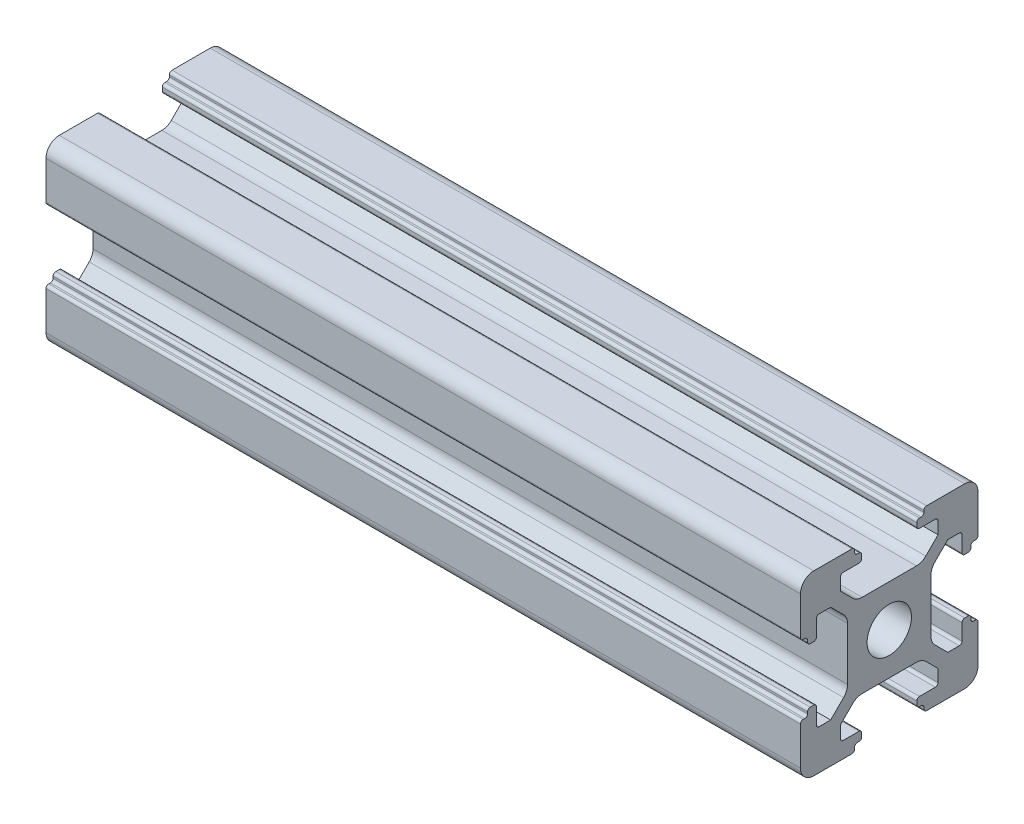
SolidWorks part; units mm, degrees
ref_plane "Front Plane" through (0, 0, 0) normal (0, 0, 1) x (1, 0, 0)
ref_plane "Top Plane" through (0, 0, 0) normal (0, 1, 0) x (1, 0, 0)
ref_plane "Right Plane" through (0, 0, 0) normal (1, 0, 0) x (0, 0, -1)
sketch "Sketch1" plane through (0, 0, 0) normal (1, 0, 0) x (0, 0, -1)
  line L0 (0, 0) -> (0, 50000) construction
  line L1 (0, 0) -> (-50000, 0) construction
  line L2 (10, 4.2) -> (10, 8.5)
  line L3 (9.7, 3.9) -> (9.5, 3.9)
  line L4 (9.2, 3.6) -> (9.2, 3.4)
  line L5 (8.9, 3.1) -> (8.5, 3.1)
  line L6 (8.2, 3.4) -> (8.2, 5.2)
  line L7 (7.9, 5.5) -> (6.6, 5.5)
  line L8 (6.6, 5.5) -> (5.1393, 4.0393)
  line L9 (8.5, 10) -> (4.2, 10)
  line L10 (3.9, 9.7) -> (3.9, 9.5)
  line L11 (3.6, 9.2) -> (3.4, 9.2)
  line L12 (3.1, 8.9) -> (3.1, 8.5)
  line L13 (3.4, 8.2) -> (5.2, 8.2)
  line L14 (5.5, 7.9) -> (5.5, 6.5213)
  line L15 (5.5, 6.5213) -> (4.118, 5.1393)
  line L16 (4.7, 2.9787) -> (4.7, -2.9787)
  line L17 (3.0574, 4.7) -> (-3.0574, 4.7)
  line L18 (-4.7, 2.9787) -> (-4.7, -2.9787)
  line L19 (-5.5, 6.5213) -> (-4.118, 5.1393)
  line L20 (-5.5, 7.9) -> (-5.5, 6.5213)
  line L21 (-3.4, 8.2) -> (-5.2, 8.2)
  line L22 (-3.1, 8.9) -> (-3.1, 8.5)
  line L23 (-3.6, 9.2) -> (-3.4, 9.2)
  line L24 (-3.9, 9.7) -> (-3.9, 9.5)
  line L25 (-8.5, 10) -> (-4.2, 10)
  line L26 (-6.6, 5.5) -> (-5.1393, 4.0393)
  line L27 (-7.9, 5.5) -> (-6.6, 5.5)
  line L28 (-8.2, 3.4) -> (-8.2, 5.2)
  line L29 (-8.9, 3.1) -> (-8.5, 3.1)
  line L30 (-9.2, 3.6) -> (-9.2, 3.4)
  line L31 (-9.7, 3.9) -> (-9.5, 3.9)
  line L32 (-10, 4.2) -> (-10, 8.5)
  line L33 (-10, -4.2) -> (-10, -8.5)
  line L34 (-9.7, -3.9) -> (-9.5, -3.9)
  line L35 (-9.2, -3.6) -> (-9.2, -3.4)
  line L36 (-8.9, -3.1) -> (-8.5, -3.1)
  line L37 (-8.2, -3.4) -> (-8.2, -5.2)
  line L38 (-7.9, -5.5) -> (-6.6, -5.5)
  line L39 (-6.6, -5.5) -> (-5.1393, -4.0393)
  line L40 (-8.5, -10) -> (-4.2, -10)
  line L41 (-3.9, -9.7) -> (-3.9, -9.5)
  line L42 (-3.6, -9.2) -> (-3.4, -9.2)
  line L43 (-3.1, -8.9) -> (-3.1, -8.5)
  line L44 (-3.4, -8.2) -> (-5.2, -8.2)
  line L45 (-5.5, -7.9) -> (-5.5, -6.5213)
  line L46 (-5.5, -6.5213) -> (-4.118, -5.1393)
  line L47 (3.0574, -4.7) -> (-3.0574, -4.7)
  line L48 (5.5, -6.5213) -> (4.118, -5.1393)
  line L49 (5.5, -7.9) -> (5.5, -6.5213)
  line L50 (3.4, -8.2) -> (5.2, -8.2)
  line L51 (3.1, -8.9) -> (3.1, -8.5)
  line L52 (3.6, -9.2) -> (3.4, -9.2)
  line L53 (3.9, -9.7) -> (3.9, -9.5)
  line L54 (8.5, -10) -> (4.2, -10)
  line L55 (6.6, -5.5) -> (5.1393, -4.0393)
  line L56 (7.9, -5.5) -> (6.6, -5.5)
  line L57 (8.2, -3.4) -> (8.2, -5.2)
  line L58 (8.9, -3.1) -> (8.5, -3.1)
  line L59 (9.2, -3.6) -> (9.2, -3.4)
  line L60 (9.7, -3.9) -> (9.5, -3.9)
  line L61 (10, -4.2) -> (10, -8.5)
  circle A0 centre (0, 0) radius 2.5
  arc A1 (10, 8.5) -> (8.5, 10) centre (8.5, 8.5) ccw
  arc A2 (9.7, 3.9) -> (10, 4.2) centre (9.7, 4.2) ccw
  arc A3 (9.5, 3.9) -> (9.2, 3.6) centre (9.5, 3.6) ccw
  arc A4 (9.2, 3.4) -> (8.9, 3.1) centre (8.9, 3.4) cw
  arc A5 (8.5, 3.1) -> (8.2, 3.4) centre (8.5, 3.4) cw
  arc A6 (8.2, 5.2) -> (7.9, 5.5) centre (7.9, 5.2) ccw
  arc A7 (5.2, 8.2) -> (5.5, 7.9) centre (5.2, 7.9) cw
  arc A8 (3.1, 8.5) -> (3.4, 8.2) centre (3.4, 8.5) ccw
  arc A9 (3.4, 9.2) -> (3.1, 8.9) centre (3.4, 8.9) ccw
  arc A10 (4.2, 10) -> (3.9, 9.7) centre (4.2, 9.7) ccw
  arc A11 (3.9, 9.5) -> (3.6, 9.2) centre (3.6, 9.5) cw
  arc A12 (4.7, 2.9787) -> (5.1393, 4.0393) centre (6.2, 2.9787) cw
  arc A13 (3.0574, 4.7) -> (4.118, 5.1393) centre (3.0574, 6.2) ccw
  arc A14 (-3.0574, 4.7) -> (-4.118, 5.1393) centre (-3.0574, 6.2) cw
  arc A15 (-4.7, 2.9787) -> (-5.1393, 4.0393) centre (-6.2, 2.9787) ccw
  arc A16 (-3.9, 9.5) -> (-3.6, 9.2) centre (-3.6, 9.5) ccw
  arc A17 (-4.2, 10) -> (-3.9, 9.7) centre (-4.2, 9.7) cw
  arc A18 (-3.4, 9.2) -> (-3.1, 8.9) centre (-3.4, 8.9) cw
  arc A19 (-3.1, 8.5) -> (-3.4, 8.2) centre (-3.4, 8.5) cw
  arc A20 (-5.2, 8.2) -> (-5.5, 7.9) centre (-5.2, 7.9) ccw
  arc A21 (-8.2, 5.2) -> (-7.9, 5.5) centre (-7.9, 5.2) cw
  arc A22 (-8.5, 3.1) -> (-8.2, 3.4) centre (-8.5, 3.4) ccw
  arc A23 (-9.2, 3.4) -> (-8.9, 3.1) centre (-8.9, 3.4) ccw
  arc A24 (-9.5, 3.9) -> (-9.2, 3.6) centre (-9.5, 3.6) cw
  arc A25 (-9.7, 3.9) -> (-10, 4.2) centre (-9.7, 4.2) cw
  arc A26 (-10, 8.5) -> (-8.5, 10) centre (-8.5, 8.5) cw
  arc A27 (-10, -8.5) -> (-8.5, -10) centre (-8.5, -8.5) ccw
  arc A28 (-9.7, -3.9) -> (-10, -4.2) centre (-9.7, -4.2) ccw
  arc A29 (-9.5, -3.9) -> (-9.2, -3.6) centre (-9.5, -3.6) ccw
  arc A30 (-9.2, -3.4) -> (-8.9, -3.1) centre (-8.9, -3.4) cw
  arc A31 (-8.5, -3.1) -> (-8.2, -3.4) centre (-8.5, -3.4) cw
  arc A32 (-8.2, -5.2) -> (-7.9, -5.5) centre (-7.9, -5.2) ccw
  arc A33 (-5.2, -8.2) -> (-5.5, -7.9) centre (-5.2, -7.9) cw
  arc A34 (-3.1, -8.5) -> (-3.4, -8.2) centre (-3.4, -8.5) ccw
  arc A35 (-3.4, -9.2) -> (-3.1, -8.9) centre (-3.4, -8.9) ccw
  arc A36 (-4.2, -10) -> (-3.9, -9.7) centre (-4.2, -9.7) ccw
  arc A37 (-3.9, -9.5) -> (-3.6, -9.2) centre (-3.6, -9.5) cw
  arc A38 (-4.7, -2.9787) -> (-5.1393, -4.0393) centre (-6.2, -2.9787) cw
  arc A39 (-3.0574, -4.7) -> (-4.118, -5.1393) centre (-3.0574, -6.2) ccw
  arc A40 (3.0574, -4.7) -> (4.118, -5.1393) centre (3.0574, -6.2) cw
  arc A41 (4.7, -2.9787) -> (5.1393, -4.0393) centre (6.2, -2.9787) ccw
  arc A42 (3.9, -9.5) -> (3.6, -9.2) centre (3.6, -9.5) ccw
  arc A43 (4.2, -10) -> (3.9, -9.7) centre (4.2, -9.7) cw
  arc A44 (3.4, -9.2) -> (3.1, -8.9) centre (3.4, -8.9) cw
  arc A45 (3.1, -8.5) -> (3.4, -8.2) centre (3.4, -8.5) cw
  arc A46 (5.2, -8.2) -> (5.5, -7.9) centre (5.2, -7.9) ccw
  arc A47 (8.2, -5.2) -> (7.9, -5.5) centre (7.9, -5.2) cw
  arc A48 (8.5, -3.1) -> (8.2, -3.4) centre (8.5, -3.4) ccw
  arc A49 (9.2, -3.4) -> (8.9, -3.1) centre (8.9, -3.4) ccw
  arc A50 (9.5, -3.9) -> (9.2, -3.6) centre (9.5, -3.6) cw
  arc A51 (9.7, -3.9) -> (10, -4.2) centre (9.7, -4.2) cw
  arc A52 (10, -8.5) -> (8.5, -10) centre (8.5, -8.5) cw
  point P24 (10, 10)
  point P41 (3.1, 9.2)
  point P44 (3.9, 10)
  point P94 (4.7, 0)
  point P95 (0, 4.7)
  point P175 (0, -4.7)
  point P176 (-4.7, 0)
  dimension "D1" = 5
  dimension "D15" = 1.5
  dimension "D16" = 0.3
  dimension "D19" = 1.5
  dimension "D2" = 20
  dimension "D3" = 1.8
  dimension "D4" = 6.2
  dimension "D5" = 3.4
  dimension "D6" = 11
  dimension "D7" = 6.1
  dimension "D8" = 1.5
  dimension "D9" = 20
  dimension "D10" = 6.1
  dimension "D11" = 6.2
  dimension "D12" = 11
  dimension "D13" = 45
  dimension "D14" = 1.8
  dimension "D17" = 3.5
  dimension "D18" = 3.5
extrude "Boss-Extrude2" add sketch "Sketch1" along normal mid plane 85
